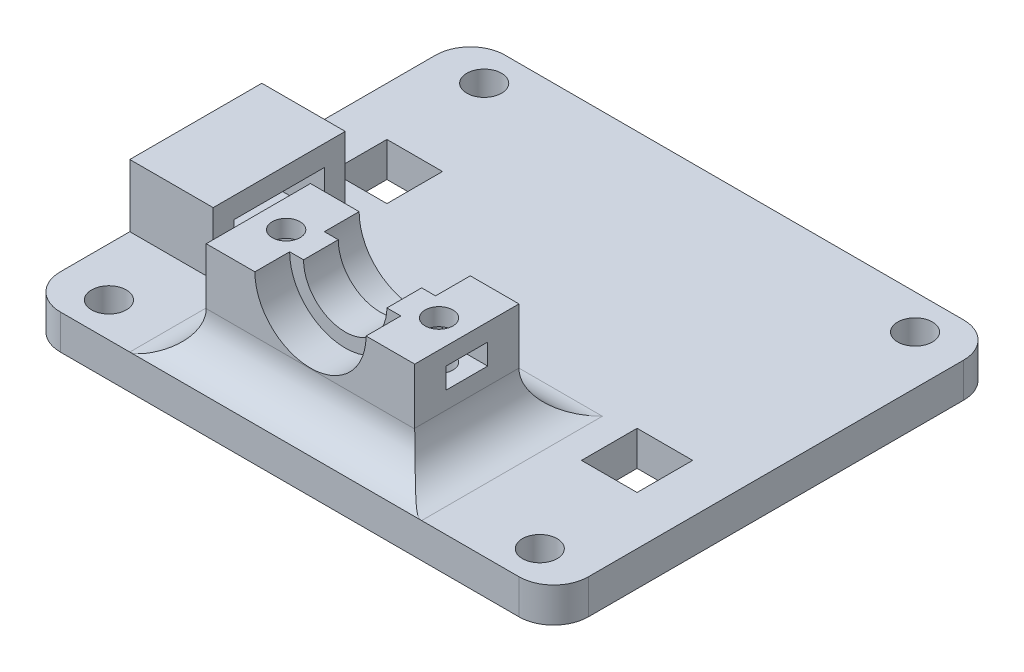
SolidWorks part; units mm, degrees
ref_plane "Front Plane" through (0, 0, 0) normal (0, 0, 1) x (1, 0, 0)
ref_plane "Top Plane" through (0, 0, 0) normal (0, 1, 0) x (1, 0, 0)
ref_plane "Right Plane" through (0, 0, 0) normal (1, 0, 0) x (0, 0, -1)
sketch "Sketch1" plane through (0, 0, 0) normal (0, 1, 0) x (1, 0, 0)
  line L0 (5.9158, 17.5579) -> (5.9158, -46.4421)
  line L1 (-32.0842, 17.5579) -> (43.9158, 17.5579)
  line L2 (-32.0842, 17.5579) -> (-32.0842, -46.4421)
  line L3 (-32.0842, -46.4421) -> (43.9158, -46.4421)
  line L4 (43.9158, 17.5579) -> (43.9158, -46.4421)
  circle A0 centre (36.9158, 12.5579) radius 2.5
  circle A1 centre (-25.0842, 12.5579) radius 2.5
  circle A2 centre (36.9158, -41.4421) radius 2.5
  circle A3 centre (-25.0842, -41.4421) radius 2.5
  point P12 (0, 0)
  dimension "D3" = 5
  dimension "D1" = 76
  dimension "D2" = 64
  dimension "D4" = 7
  dimension "D5" = 7
  dimension "D6" = 5
  dimension "D7" = 5
  dimension "D8" = 7
  dimension "D9" = 7
  dimension "D10" = 5
extrude "Boss-Extrude1" add sketch "Sketch1" along normal blind 5 contours L0 L1 L2 L3 A3 A1 | L0 L3 L4 L1 A0 region at (24.7188, 0, 14.4421) region at (-12.8873, 0, 14.4421)
sketch "Sketch2" plane through (0, 5, 0) normal (0, 1, 0) x (1, 0, 0)
  line L2 (-32.0842, -46.4421) -> (43.9158, -46.4421) construction
  line L4 (-11.0842, -26.4421) -> (18.9158, -26.4421)
  line L5 (-11.0842, -26.4421) -> (-11.0842, -41.4421)
  line L6 (-11.0842, -41.4421) -> (18.9158, -41.4421)
  line L7 (18.9158, -26.4421) -> (18.9158, -41.4421)
  dimension "D1" = 30
  dimension "D2" = 15
  dimension "D4" = 5
extrude "Boss-Extrude2" add sketch "Sketch2" along normal blind 14
sketch "Sketch3" plane through (0, 0, 41.4421) normal (0, 0, 1) x (1, 0, 0)
  line L0 (-11.0842, 19) -> (18.9158, 19) construction
  circle A1 centre (3.9158, 19) radius 6
extrude "Cut-Extrude1" cut sketch "Sketch3" against normal through all
sketch "Sketch4" plane through (0, 0, 41.4421) normal (0, 0, 1) x (1, 0, 0)
  line L0 (-2.0842, 19) -> (9.9158, 19)
  circle A0 centre (3.9158, 19) radius 8
  line M1 (18.9158, 19) -> (9.9158, 19)
  arc M2 (9.9158, 19) -> (-2.0842, 19) centre (3.9158, 19) cw
  line M3 (-2.0842, 19) -> (-11.0842, 19)
extrude "Cut-Extrude2" cut sketch "Sketch4" against normal blind 5 contours A0 M3 M1 M2 region at (3.9158, 12.8211, 41.4421)
sketch "Sketch5" plane through (0, 0, 26.4421) normal (0, 0, -1) x (-1, 0, 0)
  line L0 (-9.9158, 19) -> (2.0842, 19)
  circle A0 centre (-3.9158, 19) radius 8
  line M1 (11.0842, 19) -> (2.0842, 19)
  arc M2 (2.0842, 19) -> (-9.9158, 19) centre (-3.9158, 19) cw
  line M3 (-9.9158, 19) -> (-18.9158, 19)
extrude "Cut-Extrude3" cut sketch "Sketch5" against normal blind 5 contours A0 M3 M1 M2 region at (3.9158, 12.8211, 26.4421)
fillet "Fillet1" radius 6 4 edges at (18.9158, 5, 33.9421) (3.9158, 5, 41.4421) (3.9158, 5, 26.4421) (-11.0842, 5, 33.9421)
sketch "Sketch6" plane through (0, 5, 0) normal (0, 1, 0) x (1, 0, 0)
  line L0 (43.9158, 17.5579) -> (43.9158, -46.4421) construction
  line L1 (28.9158, -19.4421) -> (36.9158, -19.4421)
  line L2 (28.9158, -19.4421) -> (28.9158, -27.4421)
  line L3 (28.9158, -27.4421) -> (36.9158, -27.4421)
  line L4 (36.9158, -19.4421) -> (36.9158, -27.4421)
  line L5 (24.9158, -46.4421) -> (43.9158, -46.4421) construction
  line L6 (-32.0842, 17.5579) -> (-32.0842, -46.4421) construction
  line L7 (-25.0842, -1.4421) -> (-17.0842, -1.4421)
  line L8 (-25.0842, -1.4421) -> (-25.0842, -9.4421)
  line L9 (-25.0842, -9.4421) -> (-17.0842, -9.4421)
  line L10 (-17.0842, -1.4421) -> (-17.0842, -9.4421)
  line L11 (-32.0842, 17.5579) -> (43.9158, 17.5579) construction
  dimension "D1" = 15
  dimension "D2" = 19
  dimension "D3" = 8
  dimension "D4" = 8
  dimension "D5" = 15
  dimension "D6" = 19
  dimension "D7" = 8
  dimension "D8" = 8
extrude "Cut-Extrude4" cut sketch "Sketch6" against normal through all
sketch "Sketch7" plane through (0, 5, 0) normal (0, 1, 0) x (1, 0, 0)
  line L0 (-32.0842, 17.5579) -> (-32.0842, -46.4421) construction
  line L1 (-32.0842, -12.4421) -> (-20.0842, -12.4421)
  line L2 (-32.0842, -12.4421) -> (-32.0842, -31.4421)
  line L3 (-32.0842, -31.4421) -> (-20.0842, -31.4421)
  line L4 (-20.0842, -12.4421) -> (-20.0842, -31.4421)
  line L5 (-32.0842, -46.4421) -> (-17.0842, -46.4421) construction
  dimension "D1" = 19
  dimension "D2" = 12
  dimension "D3" = 0
  dimension "D4" = 15
extrude "Boss-Extrude3" add sketch "Sketch7" along normal blind 9 contours L4 L3 L2 L1
sketch "Sketch9" plane through (-32.0842, 0, 0) normal (-1, 0, 0) x (0, 0, 1)
  line L0 (12.4421, 14) -> (12.4421, 5) construction
  line L1 (15.4421, 11) -> (28.4421, 11)
  line L2 (15.4421, 11) -> (15.4421, 5)
  line L3 (15.4421, 5) -> (28.4421, 5)
  line L4 (28.4421, 11) -> (28.4421, 5)
  line L5 (12.4421, 14) -> (31.4421, 14) construction
  point P4 (12.4421, 9.5)
  dimension "D1" = 6
  dimension "D2" = 13
  dimension "D3" = 3
  dimension "D4" = 3
extrude "Cut-Extrude5" cut sketch "Sketch9" against normal blind 14
fillet "Fillet3" radius 5 4 edges at (-32.0842, 2.5, 46.4421) (-32.0842, 2.5, -17.5579) (43.9158, 2.5, 46.4421) (43.9158, 2.5, -17.5579)
sketch "Sketch10" plane through (0, 19, 0) normal (0, 1, 0) x (1, 0, 0)
  line L0 (-11.0842, -33.9421) -> (24.9158, -33.9421)
  line L1 (-11.0842, -26.4421) -> (-11.0842, -41.4421) construction
  line L2 (24.9158, -20.4421) -> (24.9158, -46.4421) construction
  line L3 (3.9158, -26.4421) -> (3.9158, -41.4421)
  line L4 (-4.0842, -41.4421) -> (11.9158, -41.4421) construction
  circle A0 centre (-7.0842, -33.9421) radius 2
  circle A1 centre (14.9158, -33.9421) radius 2
  dimension "D1" = 11
extrude "Cut-Extrude6" cut sketch "Sketch10" against normal blind 9 contours L0 A0 | L0 A0 | A1 L0 | A1 L0 region at (-7.0842, 19, 33.0933) region at (14.9158, 19, 33.0933) region at (14.9158, 19, 34.7909) region at (-7.0842, 19, 34.7909)
sketch "Sketch11" plane through (-11.0842, 0, 0) normal (-1, 0, 0) x (0, 0, 1)
  line L0 (41.4421, 15) -> (26.4421, 15)
  line L1 (41.4421, 19) -> (41.4421, 11) construction
  line L2 (26.4421, 19) -> (26.4421, 11) construction
  line L3 (33.9421, 19) -> (33.9421, 11)
  line L4 (26.4421, 19) -> (41.4421, 19) construction
  line L5 (26.4421, 11) -> (41.4421, 11) construction
  line L7 (30.9421, 16.5) -> (36.9421, 16.5)
  line L8 (30.9421, 16.5) -> (30.9421, 13.5)
  line L9 (30.9421, 13.5) -> (36.9421, 13.5)
  line L10 (36.9421, 16.5) -> (36.9421, 13.5)
  dimension "D1" = 6
  dimension "D2" = 3
  dimension "D3" = 1.5
  dimension "D4" = 3
extrude "Cut-Extrude7" cut sketch "Sketch11" against normal blind 6.5 contours L7 L8 L0 L3 | L10 L7 L3 L0 | L10 L0 L3 L9 | L8 L9 L3 L0 region at (-11.0842, 14.25, 35.4421) region at (-11.0842, 15.75, 35.4421) region at (-11.0842, 14.25, 32.4421) region at (-11.0842, 15.75, 32.4421)
sketch "Sketch13" plane through (18.9158, 0, 0) normal (1, 0, 0) x (0, 0, -1)
  line L0 (-41.4421, 15) -> (-26.4421, 15)
  line L1 (-41.4421, 19) -> (-41.4421, 11) construction
  line L2 (-26.4421, 19) -> (-26.4421, 11) construction
  line L3 (-33.9421, 19) -> (-33.9421, 11)
  line L4 (-41.4421, 19) -> (-26.4421, 19) construction
  line L5 (-41.4421, 11) -> (-26.4421, 11) construction
  line L7 (-36.9421, 16.5) -> (-30.9421, 16.5)
  line L8 (-36.9421, 16.5) -> (-36.9421, 13.5)
  line L9 (-36.9421, 13.5) -> (-30.9421, 13.5)
  line L10 (-30.9421, 16.5) -> (-30.9421, 13.5)
  dimension "D1" = 6
  dimension "D2" = 3
  dimension "D3" = 1.5
  dimension "D4" = 3
extrude "Cut-Extrude8" cut sketch "Sketch13" against normal blind 6.5 contours L7 L8 L0 L3 | L10 L7 L3 L0 | L10 L0 L3 L9 | L8 L9 L3 L0 region at (18.9158, 15.75, 35.4421) region at (18.9158, 14.25, 35.4421) region at (18.9158, 15.75, 32.4421) region at (18.9158, 14.25, 32.4421)
